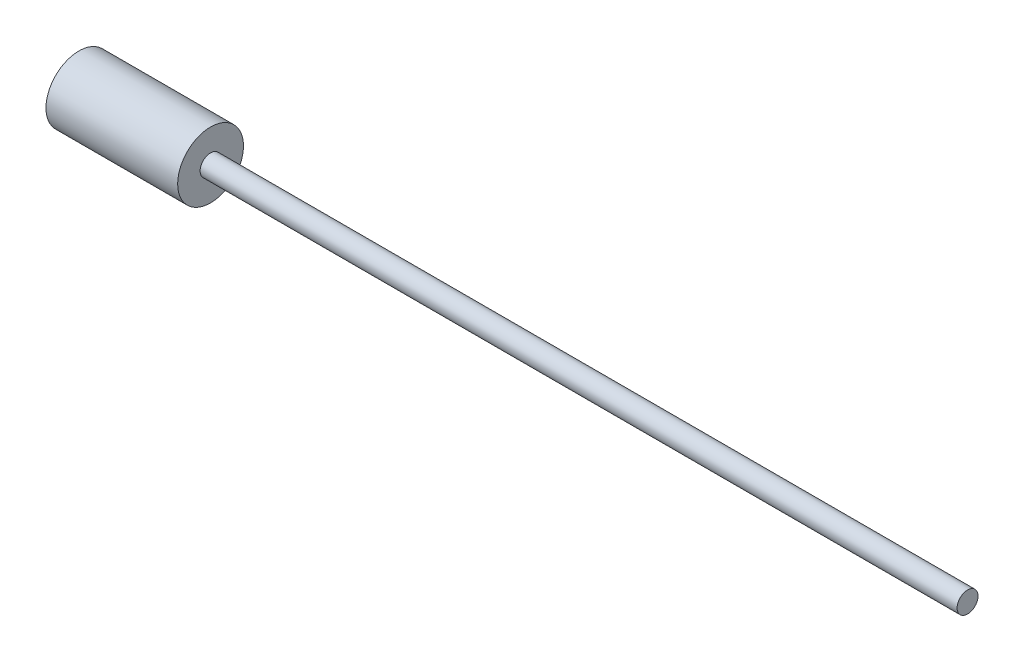
SolidWorks part; units mm, degrees
ref_plane "Front Plane" through (0, 0, 0) normal (0, 0, 1) x (1, 0, 0)
ref_plane "Top Plane" through (0, 0, 0) normal (0, 1, 0) x (1, 0, 0)
ref_plane "Right Plane" through (0, 0, 0) normal (1, 0, 0) x (0, 0, -1)
sketch "TC_Probe Sketch" plane through (0, 0, 0) normal (0, 0, 1) x (1, 0, 0)
  line L0 (-1000, 0) -> (1000, 0) construction
  line L1 (90, 0) -> (90, 1.5875)
  line L2 (90, 1.5875) -> (-25, 1.5875)
  line L3 (-25, 1.5875) -> (-25, 5)
  line L4 (-25, 5) -> (-45, 5)
  line L5 (-45, 5) -> (-45, 0)
  line L6 (-45, 0) -> (90, 0)
revolve "TC_Probe" add sketch "TC_Probe Sketch" angle 360 about L0
ref_axis "Engine Axis" through (96.75, 0, 0) along (-1, 0, 0)
